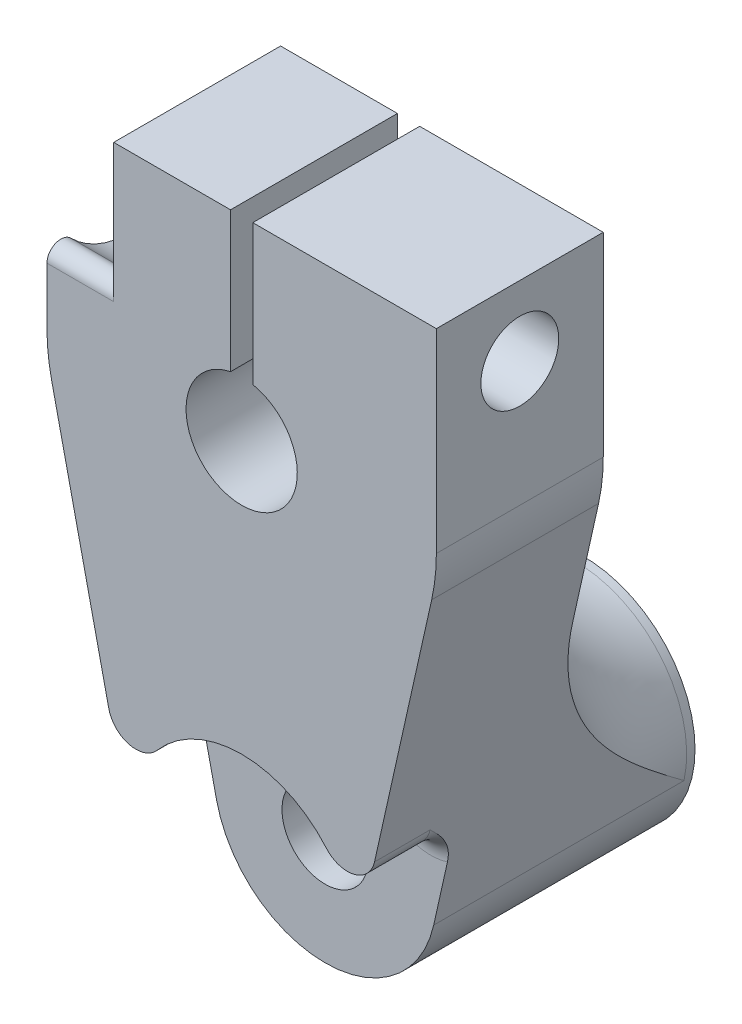
SolidWorks part; units mm, degrees
material "ABS"
ref_plane "前视基准面" through (0, 0, 0) normal (0, 0, 1) x (1, 0, 0)
ref_plane "上视基准面" through (0, 0, 0) normal (0, 1, 0) x (1, 0, 0)
ref_plane "右视基准面" through (0, 0, 0) normal (1, 0, 0) x (0, 0, -1)
other "Configuration Table"
sketch "草图1" plane through (0, 0, 0) normal (0, 0, 1) x (1, 0, 0)
  line L0 (-12.0241, 0) -> (2.8181, 0) construction
  line L1 (0, 5.1549) -> (0, -4.1685) construction
  circle A0 centre (0, 0) radius 1.55
  circle A1 centre (0, 0) radius 4
  dimension "D1" = 3.1
  dimension "D2" = 8
extrude "凸台-拉伸1" add sketch "草图1" along normal blind 6.3
sketch "草图2" plane through (0, 0, 6.3) normal (0, 0, 1) x (1, 0, 0)
  line L0 (-6.8313, 12.2202) -> (-3.9036, -0.8729)
  line L1 (6.8313, 12.2202) -> (3.9036, -0.8729)
  line L2 (-7, 13.7477) -> (-7, 20.7477)
  line L3 (-7, 20.7477) -> (0, 20.7477)
  line L4 (0, 20.7477) -> (7, 20.7477)
  line L5 (7, 20.7477) -> (7, 13.7477)
  circle A0 centre (0, 13.7477) radius 2
  arc A1 (6.8313, 12.2202) -> (7, 13.7477) centre (0, 13.7477) ccw
  circle A2 centre (0, 0) radius 4 construction
  arc A4 (-3.9036, -0.8729) -> (3.9036, -0.8729) centre (0, 0) ccw
  arc A5 (-7, 13.7477) -> (-6.8313, 12.2202) centre (0, 13.7477) ccw
  circle M3 centre (0, 0) radius 4
  circle M4 centre (0, 0) radius 1.55
  dimension "D1" = 13.7477
  dimension "D2" = 4
  dimension "D3" = 14
extrude "凸台-拉伸2" add sketch "草图2" along normal blind 6 contours L1 A1 L0 A0 M3 | M3 M4 region at (-6.7017, 13.0076, 6.3) region at (-0.4267, 3.8634, 6.3)
sketch "草图3" plane through (0, 0, 12.3) normal (0, 0, 1) x (1, 0, 0)
  line L0 (0, 23.4906) -> (0, 9.0683) construction
  line L1 (-0.4, 27.5318) -> (0.4, 27.5318)
  line L2 (-0.4, 27.5318) -> (-0.4, 15.1807)
  line L3 (-0.4, 15.1807) -> (0.4, 15.1807)
  line L4 (0.4, 27.5318) -> (0.4, 15.1807)
  dimension "D1" = 0.8
extrude "切除-拉伸1" cut sketch "草图3" against normal through all
ref_plane "基准面1" through (-4.6, 0, 0) normal (-1, 0, 0) x (0, 0, 1)
sketch "草图4" plane through (-4.6, 0, 0) normal (-1, 0, 0) x (0, 0, 1)
  line L0 (12.3, 12.2202) -> (6.3, 12.2202) construction
  line L1 (12.3, 20.7363) -> (6.3, 20.7363) construction
  line L2 (6.3, 18.2363) -> (6.3, 22.5741)
  line L3 (6.3, 22.5741) -> (12.3, 22.5741)
  line L4 (12.3, 22.5741) -> (12.3, 18.2363)
  arc A0 (6.3, 18.2363) -> (12.3, 18.2363) centre (9.3, 18.2363) ccw
  circle A1 centre (9.3, 18.2363) radius 1.6
  point P6 (9.3, 12.2202)
  dimension "D1" = 6
  dimension "D2" = 3.2
  dimension "D3" = 2.5
extrude "切除-拉伸2" cut sketch "草图4" along normal through all contours A1 | A0 A1 region at (-4.6, 20.4052, 6.3948) region at (-4.6, 18.2363, 9.3)
sketch "草图5" plane through (-4.6, 0, 0) normal (-1, 0, 0) x (0, 0, 1)
  circle A0 centre (9.3, 18.2363) radius 1.6
  arc A1 (6.3, 18.2363) -> (12.3, 18.2363) centre (9.3, 18.2363) ccw construction
  dimension "D1" = 3.2
extrude "切除-拉伸3" cut sketch "草图5" against normal up to next
sketch "草图6" plane through (0.4, 0, 0) normal (-1, 0, 0) x (0, 0, 1)
  circle A0 centre (9.3, 18.2363) radius 1.4
  circle A1 centre (9.3, 18.2363) radius 1.6 construction
  dimension "D1" = 2.8
extrude "切除-拉伸4" cut sketch "草图6" against normal through all
fillet "圆角1" radius 0.5 2 edges at (-5.8, 18.2363, 12.3) (-5.8, 18.2363, 6.3)
fillet "圆角2" radius 6 1 edges at (0, 4, 6.3)
sketch "草图7" plane through (0, 0, 12.3) normal (0, 0, 1) x (1, 0, 0)
  circle A0 centre (0, 0) radius 4
extrude "切除-拉伸5" cut sketch "草图7" against normal blind 3
fillet "圆角3" radius 1 2 edges at (-3.9036, -0.8729, 10.8) (3.9036, -0.8729, 10.8)
fillet "圆角4" radius 1 3 edges at (4.0418, 2.2785, 9.3) (-4.0418, 2.2785, 9.3) (0, 4, 9.3)
